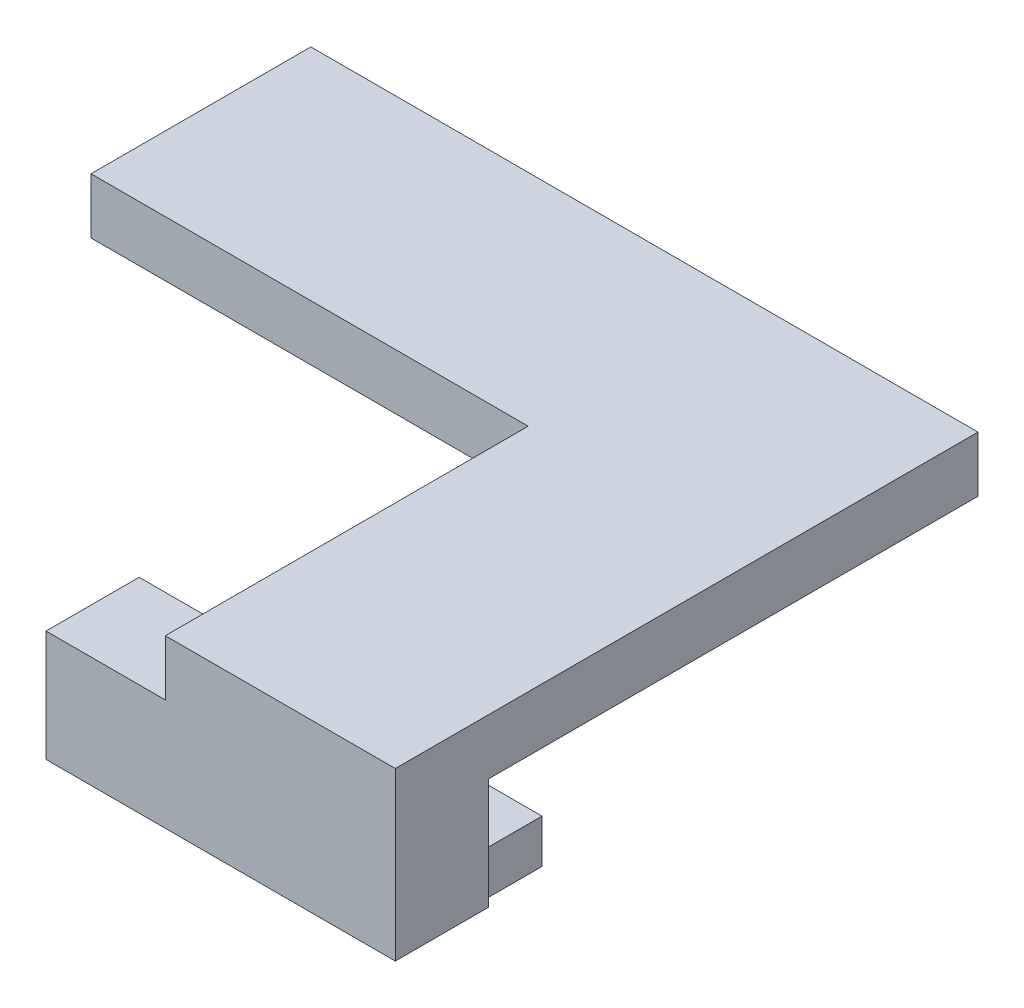
SolidWorks part; units mm, degrees
ref_plane "Front Plane" through (0, 0, 0) normal (0, 0, 1) x (1, 0, 0)
ref_plane "Top Plane" through (0, 0, 0) normal (0, 1, 0) x (1, 0, 0)
ref_plane "Right Plane" through (0, 0, 0) normal (1, 0, 0) x (0, 0, -1)
sketch "Sketch1" plane through (0, 0, 0) normal (0, 1, 0) x (1, 0, 0)
  line L1 (-60.2764, 19.703) -> (15.9236, 19.703)
  line L2 (-60.2764, 19.703) -> (-60.2764, -5.4001)
  line L3 (-60.2764, -5.4001) -> (-10.347, -5.4001)
  line L4 (15.9236, 19.703) -> (15.9236, -5.4001)
  line L6 (15.9236, -5.4001) -> (15.9236, -46.8492)
  line L7 (15.9236, -46.8492) -> (-10.347, -46.8492)
  line L8 (-10.347, -5.4001) -> (-10.347, -46.8492)
  dimension "D1" = 26.2706
  dimension "D2" = 76.2
extrude "Boss-Extrude1" add sketch "Sketch1" along normal blind 6.35
sketch "Sketch2" plane through (15.9236, 0, 0) normal (1, 0, 0) x (0, 0, -1)
  line L1 (19.703, 6.35) -> (-46.8492, 6.35)
  line L2 (19.703, 6.35) -> (19.703, 0)
  line L3 (19.703, 0) -> (-46.8492, 0)
  line L4 (-46.8492, 6.35) -> (-46.8492, 0)
sketch "Sketch5" plane through (0, 0, 0) normal (0, -1, 0) x (1, 0, 0)
  line L1 (15.9236, 46.8492) -> (-23.9712, 46.8492)
  line L2 (15.9236, 46.8492) -> (15.9236, 36.2101)
  line L3 (15.9236, 36.2101) -> (-23.9712, 36.2101)
  line L4 (-23.9712, 46.8492) -> (-23.9712, 36.2101)
extrude "Boss-Extrude5" add sketch "Sketch5" along normal blind 12.7
sketch "Sketch6" plane through (0, 0, 36.2101) normal (0, 0, -1) x (-1, 0, 0)
  line L0 (9.4764, -6.35) -> (9.4764, -11.9566) construction
  line L1 (22.1764, -11.9566) -> (9.4764, -11.9566)
  line L2 (22.1764, -11.9566) -> (22.1764, -6.971)
  line L3 (22.1764, -6.971) -> (9.4764, -6.971)
  line L4 (9.4764, -11.9566) -> (9.4764, -6.971)
  line L5 (-15.6891, -6.35) -> (-15.6891, -12.7) construction
  line L6 (-3.2236, -11.9566) -> (-15.6891, -11.9566)
  line L7 (-3.2236, -11.9566) -> (-3.2236, -6.971)
  line L8 (-3.2236, -6.971) -> (-15.6891, -6.971)
  line L9 (-15.6891, -11.9566) -> (-15.6891, -6.971)
extrude "Boss-Extrude6" add sketch "Sketch6" along normal blind 6.35
